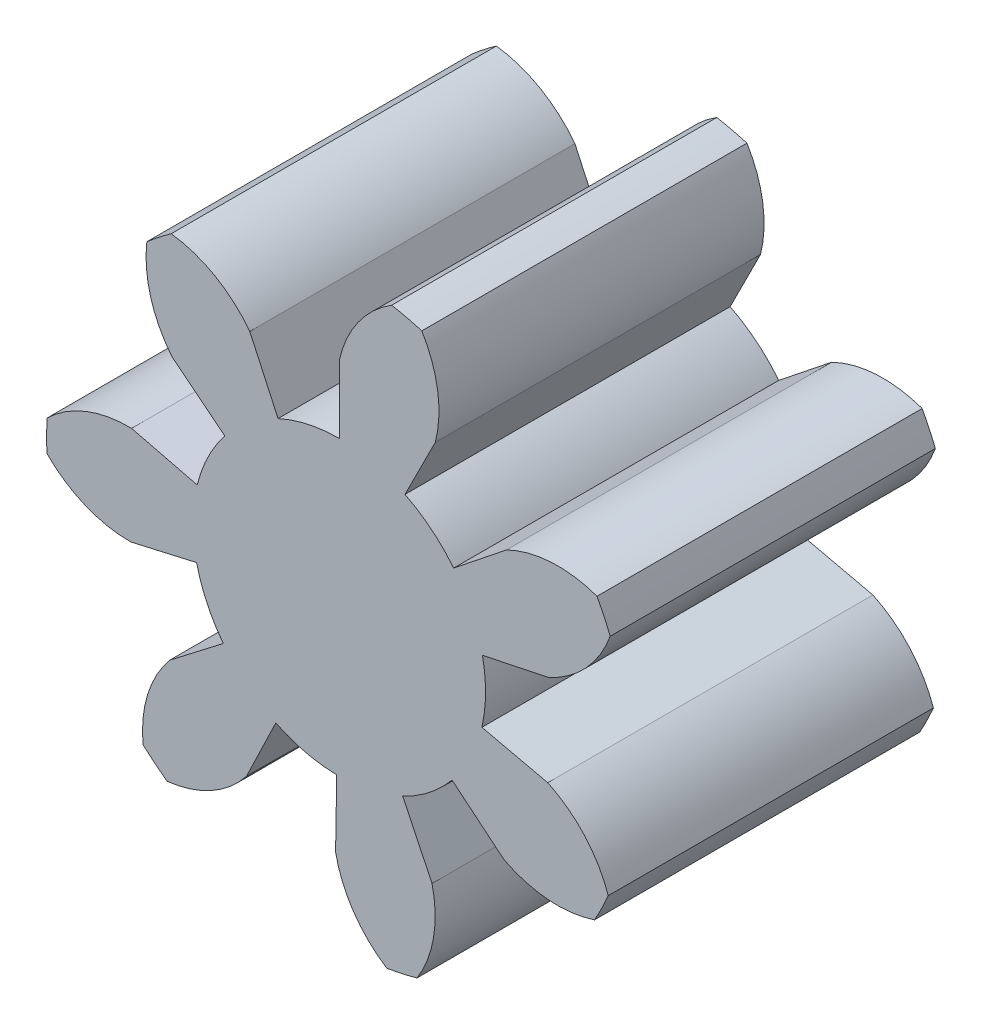
SolidWorks part; units mm, degrees
ref_plane "Plan de face" through (0, 0, 0) normal (0, 0, 1) x (1, 0, 0)
ref_plane "Plan de dessus" through (0, 0, 0) normal (0, 1, 0) x (1, 0, 0)
ref_plane "Plan de droite" through (0, 0, 0) normal (1, 0, 0) x (0, 0, -1)
sketch "Esquisse1" plane through (0, 0, 0) normal (0, 0, 1) x (1, 0, 0)
  circle A0 centre (0, 0) radius 7
  circle A1 centre (0, 0) radius 9
  circle A2 centre (0, 0) radius 4.5
  circle A3 centre (0, 0) radius 5
  circle A4 centre (0, 0) radius 6.5778
  dimension "Pitch Circle" = 14
  dimension "Addendum Circle" = 18
  dimension "Root Circle" = 9
  dimension "Clearence Circle" = 10
  dimension "Base Circle" = 13.1557
sketch "Involute" plane through (0, 0, 0) normal (0, 0, 1) x (1, 0, 0)
  line L0 (0, 0) -> (0, 6.5778)
  line L1 (0, 0) -> (3.2889, 5.6966) construction
  line L2 (0, 0) -> (5.6966, 3.2889) construction
  line L3 (0, 0) -> (6.5778, 0) construction
  line L4 (6.5778, 0) -> (6.5778, 10.3325) construction
  line L5 (5.6966, 3.2889) -> (2.2524, 9.2544) construction
  line L6 (3.2889, 5.6966) -> (0.3062, 7.4187) construction
  line L7 (0, 0) -> (3.0372, 6.3068) construction
  line L8 (5.4728, 4.3644) -> (0, 0)
  line L9 (1.6164, 6.8108) -> (0, 0) construction
  circle A0 centre (0, 0) radius 6.5778 construction
  circle A1 centre (0, 0) radius 7 construction
  arc A2 (3.0372, 6.3068) -> (0.1206, 6.999) centre (0, 0) ccw
  spline S0 degree 3 poles (0, 6.5778) (0.5786, 9.2716) (4.3581, 10.336) (6.5778, 10.3325) knots 0 0 0 0 1 1 1 1
  spline S1 degree 3 poles (2.9557, 5.8764) (3.6492, 8.5429) (0.751, 11.192) (-1.2336, 12.1863) knots 0 0 0 0 1 1 1 1
  dimension "Involute Control" = 90
  dimension "Base Circle Quarter Circumference" = 10.3325
  dimension "D1" = 6.8883
  dimension "D2" = 3.4442
  dimension "Circular Pitch" = 51.429
  dimension "Involute Array" = 4
sketch "Esquisse4" plane through (0, 0, 0) normal (0, 0, 1) x (1, 0, 0)
  line L0 (0, 0) -> (0, 6.5778) construction
  line L1 (0, 6.5778) -> (0, 4.5)
  line L2 (2.9557, 5.8764) -> (2.022, 4.0201)
  arc A0 (1.6117, 8.8545) -> (2.5389, 8.6345) centre (0, 0) cw
  circle A1 centre (0, 0) radius 9 construction
  arc A2 (0, 4.5) -> (2.022, 4.0201) centre (0, 0) cw
  circle A3 centre (0, 0) radius 4.5 construction
  arc A4 (0, 6.5778) -> (1.6117, 8.8545) centre (3.5132, 5.7996) cw
  arc A5 (2.5389, 8.6345) -> (2.9557, 5.8764) centre (-0.5325, 6.7598) cw
  spline S0 degree 3 poles (0, 6.5778) (0.5786, 9.2716) (4.3581, 10.336) (6.5778, 10.3325) knots 0 0 0 0 1 1 1 1 construction
  spline S1 degree 3 poles (2.9557, 5.8764) (3.6492, 8.5429) (0.751, 11.192) (-1.2336, 12.1863) knots 0 0 0 0 1 1 1 1 construction
extrude "Boss.-Extru.1" add sketch "Esquisse4" along normal blind 10
ref_axis "Axe1" through (0, 0, 0) along (0, 0, 1)
pattern_circular "Répétition circulaire2" count 7 over 360 about axis through (0, 0, 0) along (0, 0, 1) of bodies 101
sketch "Esquisse5" plane through (0, 0, 0) normal (0, 0, 1) x (1, 0, 0)
  circle A0 centre (0, 0) radius 4.5 construction
  circle A1 centre (0, 0) radius 4.5
extrude "Boss.-Extru.2" add sketch "Esquisse5" along normal up to surface (10 mm away) up to face at (-6.6458, 0.0572, 10)
equation "\"Module\"= 2"
equation "\"Nb de dents\"= 7"
equation "\"Pressure Angle\"= 20"
equation "\"Pitch Circle@Esquisse1\"= \"Module\" * \"Nb de dents\""
equation "\"Addendum Circle@Esquisse1\"= \"Pitch Circle@Esquisse1\" + ( \"Module\" * 2 )"
equation "\"Clearence Circle@Esquisse1\"= \"Pitch Circle@Esquisse1\" - ( \"Module\" * 2 )"
equation "\"Root Circle@Esquisse1\"= \"Pitch Circle@Esquisse1\" - ( ( \"Module\" * 1.25 ) * 2 )"
equation "\"Base Circle@Esquisse1\"= \"Pitch Circle@Esquisse1\" * cos ( \"Pressure Angle\" )"
equation "\"Base Circle Quarter Circumference@Involute\" = \"Base Circle@Esquisse1\" * pI / 4"
equation "\"D1@Involute\"=\"Base Circle Quarter Circumference@Involute\"/3*2"
equation "\"D2@Involute\"=\"Base Circle Quarter Circumference@Involute\"/3"
equation "\"Circular Pitch@Involute\"=360/\"Nb de dents\""
equation "\"D1@Répétition circulaire2\"= \"Nb de dents\""
